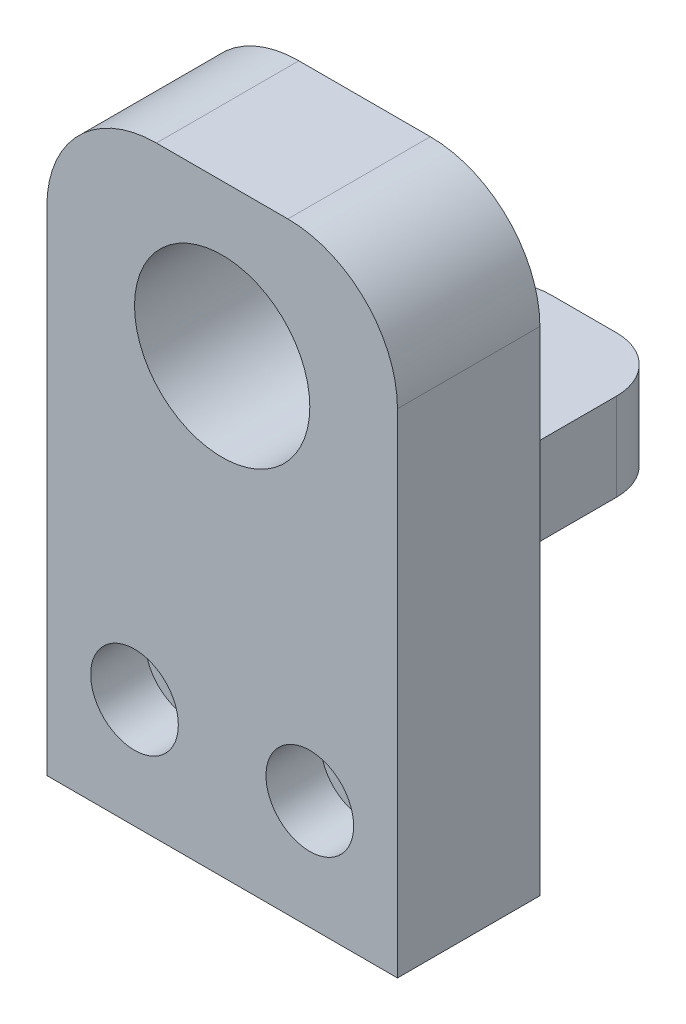
SolidWorks part; units mm, degrees
ref_plane "Alzado" through (0, 0, 0) normal (0, 0, 1) x (1, 0, 0)
ref_plane "Planta" through (0, 0, 0) normal (0, 1, 0) x (1, 0, 0)
ref_plane "Vista lateral" through (0, 0, 0) normal (1, 0, 0) x (0, 0, -1)
sketch "Croquis1" plane through (0, 0, 0) normal (0, 0, 1) x (1, 0, 0)
  line L0 (255, -10) -> (0, -10) construction
  line L1 (111.5, -10) -> (143.5, -10)
  line L2 (111.5, -10) -> (111.5, 45)
  line L3 (111.5, 45) -> (143.5, 45)
  line L4 (143.5, -10) -> (143.5, 45)
  line L5 (127.5, 31.15) -> (127.5, 45) construction
  circle A0 centre (127.5, 31.15) radius 8
  circle A1 centre (119.5, 0) radius 2.05
  circle A2 centre (135.5, 0) radius 2.05
  dimension "D1" = 16
  dimension "D4" = 4.1
  dimension "D2" = 32
  dimension "D3" = 55
  dimension "D5" = 10
  dimension "D6" = 8
extrude "Saliente-Extruir2" add sketch "Croquis1" along normal blind 13
fillet "Redondeo1" radius 10 2 edges at (111.5, 45, 6.5) (143.5, 45, 6.5)
sketch "Croquis2" plane through (0, 0, 13) normal (0, 0, 1) x (1, 0, 0)
  circle A0 centre (119.5, 0) radius 4
  circle A1 centre (135.5, 0) radius 4
  dimension "D1" = 8
extrude "Cortar-Extruir1" cut sketch "Croquis2" against normal blind 5
sketch "Croquis3" plane through (0, 0, 0) normal (0, 0, -1) x (-1, 0, 0)
  line L0 (-119.5, 10) -> (-135.5, 10) construction
  line L3 (-111.5, -10) -> (-143.5, -10) construction
  line L4 (-143.5, -10) -> (-143.5, 35) construction
  line L5 (-135.5, 10) -> (-119.5, 10)
  line L6 (-135.5, 10) -> (-135.5, 18)
  line L7 (-135.5, 18) -> (-119.5, 18)
  line L8 (-119.5, 10) -> (-119.5, 18)
  line L9 (-111.5, 35) -> (-111.5, -10) construction
  dimension "D1" = 20
  dimension "D2" = 8
  dimension "D3" = 8
  dimension "D4" = 8
extrude "Saliente-Extruir3" add sketch "Croquis3" along normal blind 20
sketch "Croquis4" plane through (0, 18, 0) normal (0, 1, 0) x (1, 0, 0)
  line L0 (127.5, 20) -> (127.5, 10) construction
  line L1 (119.5, 20) -> (135.5, 20) construction
  circle A0 centre (127.5, 10) radius 2.05
  dimension "D1" = 4.1
  dimension "D2" = 10
extrude "Cortar-Extruir2" cut sketch "Croquis4" against normal up to next
sketch "Croquis5" plane through (0, 18, 0) normal (0, 1, 0) x (1, 0, 0)
  circle A0 centre (127.5, 10) radius 4
  dimension "D1" = 8
extrude "Cortar-Extruir3" cut sketch "Croquis5" against normal blind 3
fillet "Redondeo3" radius 8 3 edges at (119.5, 14, 0) (127.5, 18, 0) (135.5, 14, 0)
fillet "Redondeo4" radius 5 2 edges at (119.5, 14, -20) (135.5, 14, -20)
